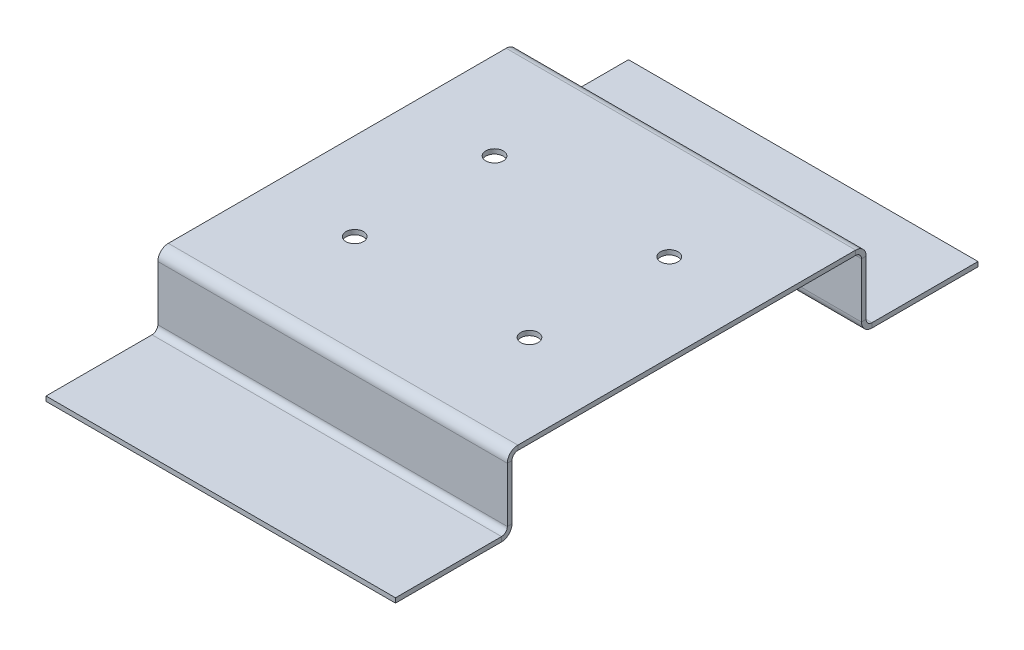
SolidWorks part; units mm, degrees
note: The reader was unsure of these and kept them because the rebuilt part matched: thickness of "Base-Flange2", "Edge-Flange1", "Edge-Flange2", "Sheet-Metal3", "Sheet-Metal4", "Sheet-Metal5", "Sheet-Metal6"; flange length of "Edge-Flange1", "Edge-Flange2".
ref_plane "Front Plane" through (0, 0, 0) normal (0, 0, 1) x (1, 0, 0)
ref_plane "Top Plane" through (0, 0, 0) normal (0, 1, 0) x (1, 0, 0)
ref_plane "Right Plane" through (0, 0, 0) normal (1, 0, 0) x (0, 0, -1)
sketch "Sketch1" plane through (0, 0, 0) normal (0, 0, 1) x (1, 0, 0)
  line L0 (0, 0) -> (20, 0)
  line L1 (20, 0) -> (20, 13)
  line L2 (20, 13) -> (80, 13)
  line L3 (80, 13) -> (80, 0)
  line L4 (80, 0) -> (100, 0)
  line L5 (0, 0.8) -> (19.2, 0.8)
  line L6 (19.2, 0.8) -> (19.2, 13.8)
  line L7 (19.2, 13.8) -> (80.8, 13.8)
  line L8 (80.8, 13.8) -> (80.8, 0.8)
  line L9 (80.8, 0.8) -> (100, 0.8)
  line L10 (0, 0) -> (0, 0.8)
  line L11 (100, 0) -> (100, 0.8)
  dimension "D2" = 20
  dimension "D3" = 20
  dimension "D4" = 60
  dimension "D5" = 13
  dimension "D1" = 0.8
sketch "Sketch7" plane through (0, 0, 0) normal (0, 1, 0) x (1, 0, 0)
  line L1 (-30, -30) -> (30, -30)
  line L2 (-30, -30) -> (-30, 30)
  line L3 (-30, 30) -> (30, 30)
  line L4 (30, -30) -> (30, 30)
  line L5 (-30, -30) -> (30, 30) construction
  line L6 (-30, 30) -> (30, -30) construction
  point P0 (0, 0)
  dimension "D1" = 60
  dimension "D2" = 60
base flange "Base-Flange2" sketch "Sketch7" thickness 0.8 reverse thickness direction no parameters "D1"=0.7366
edge flange "Edge-Flange1" sketch "Sketch14" flange profiles "Sketch14", "Sketch15" flange angle 90 flange length 13 flange position material outside bend radius 1 thickness 0.8 relief rectangular parameters "D6"=10, "D8"=1
sketch "Sketch14" plane through (0, -0.8, -30) normal (0, 0, 1) x (-1, 0, 0)
  line L2 (-30, 0) -> (-30, 12.2)
  line L3 (-30, 12.2) -> (30, 12.2)
  line L4 (30, 12.2) -> (30, 0)
  line L5 (30, 0) -> (-30, 0) construction
  line L6 (30, 0) -> (-30, 0)
sketch "Sketch15" plane through (0, -0.8, 30) normal (0, 0, -1) x (1, 0, 0)
  line L0 (30, 0) -> (-30, 0) construction
  line L1 (30, 0) -> (-30, 0)
  line L2 (30, 0) -> (30, 12.2)
  line L3 (30, 12.2) -> (-30, 12.2)
  line L4 (-30, 12.2) -> (-30, 0)
bend "EdgeBend1" bend radius 1 bend angle 90 parameters "D5"=1
bend "EdgeBend2" bend radius 1 bend angle 90 parameters "D5"=2
edge flange "Edge-Flange2" sketch "Sketch20" flange profiles "Sketch20", "Sketch21" flange angle 90 flange length 20 flange position material inside bend radius 1 thickness 0.8 relief rectangular parameters "D6"=10, "D8"=1
sketch "Sketch20" plane through (0, -13, 30.8) normal (0, -1, 0) x (1, 0, 0)
  line L2 (-30, 0) -> (-30, 19.2)
  line L3 (-30, 19.2) -> (30, 19.2)
  line L4 (30, 19.2) -> (30, 0)
  line L7 (30, 0) -> (-30, 0) construction
  line L8 (30, 0) -> (-30, 0)
sketch "Sketch21" plane through (0, -13, -30.8) normal (0, -1, 0) x (-1, 0, 0)
  line L0 (30, 0) -> (-30, 0) construction
  line L1 (30, 0) -> (-30, 0)
  line L2 (-30, 0) -> (-30, 19.2)
  line L3 (-30, 19.2) -> (30, 19.2)
  line L4 (30, 19.2) -> (30, 0)
bend "EdgeBend3" bend radius 1 bend angle 90 parameters "D5"=3
bend "EdgeBend4" bend radius 1 bend angle 90 parameters "D5"=4
sketch "Sketch22" plane through (0, 0, 0) normal (0, 1, 0) x (1, 0, 0)
  line L1 (-15, 12) -> (15, 12) construction
  line L2 (-15, 12) -> (-15, -12) construction
  line L3 (-15, -12) -> (15, -12) construction
  line L4 (15, 12) -> (15, -12) construction
  line L5 (-15, 12) -> (15, -12) construction
  line L6 (-15, -12) -> (15, 12) construction
  circle A0 centre (-15, 12) radius 1.5
  circle A1 centre (15, 12) radius 1.5
  circle A2 centre (15, -12) radius 1.5
  circle A3 centre (-15, -12) radius 1.5
  point P0 (0, 0)
  dimension "D3" = 3
  dimension "D1" = 30
  dimension "D2" = 24
extrude "Cut-Extrude2" cut sketch "Sketch22" against normal through all normal cut yes
sketch "Bend-Lines1" [suppressed] plane through (0, 0, 0) normal (0, 1, 0) x (1, 0, 0)
sketch "Bounding-Box1" [suppressed] plane through (0, 0, 0) normal (0, 1, 0) x (1, 0, 0)
sheet metal parameters "Sheet-Metal3" thickness 0.8 parameters "D1"=0.7366
flat pattern "Flat-Pattern3" [suppressed]
sketch "Bend-Lines3" plane through (0, 0, 0) normal (0, 1, 0) x (1, 0, 0)
sketch3d "Bounding-Box3" [suppressed]
  line L0 (30, -30, 0) -> (30, 30, 0) construction
  line L1 (-30, -30, 0) -> (-30, 30, 0) construction
  line L2 (30, -30, 0) -> (-30, -30, 0) construction
  line L3 (30, 30, 0) -> (-30, 30, 0) construction
sheet metal parameters "Sheet-Metal4" thickness 0.8 parameters "D1"=0.7366
flat pattern "Flat-Pattern3"
sketch "Bend-Lines3" plane through (0, 0, 0) normal (0, 1, 0) x (1, 0, 0)
  line L0 (-30, -31.0996) -> (30, -31.0996) construction
  line L1 (30, 31.0996) -> (-30, 31.0996) construction
  line L2 (-30, -31.0996) -> (30, -31.0996) construction
  line L3 (30, 31.0996) -> (-30, 31.0996) construction
sketch3d "Bounding-Box3" [suppressed]
  line L0 (-30, -43.3991, 0) -> (-30, 43.3991, 0) construction
  line L1 (30, -43.3991, 0) -> (30, 43.3991, 0) construction
  line L2 (-30, -43.3991, 0) -> (30, -43.3991, 0) construction
  line L3 (-30, 43.3991, 0) -> (30, 43.3991, 0) construction
bend of the flat pattern "Flatten-<EdgeBend1>1"
bend of the flat pattern "Flatten-<EdgeBend2>1"
sheet metal parameters "Sheet-Metal5" thickness 0.8 parameters "D1"=0.7366
flat pattern "Flat-Pattern3"
sketch "Bend-Lines3" plane through (0, 0, 0) normal (0, 1, 0) x (1, 0, 0)
  line L0 (-30, -31.0996) -> (30, -31.0996) construction
  line L1 (30, 31.0996) -> (-30, 31.0996) construction
  line L2 (-30, -31.0996) -> (30, -31.0996) construction
  line L3 (30, 31.0996) -> (-30, 31.0996) construction
  line L4 (30, 42.6987) -> (-30, 42.6987) construction
  line L5 (-30, -42.6987) -> (30, -42.6987) construction
  line L6 (30, 42.6987) -> (-30, 42.6987) construction
  line L7 (-30, -42.6987) -> (30, -42.6987) construction
sketch3d "Bounding-Box3" [suppressed]
  line L0 (-30, -61.9982, 0) -> (-30, 61.9982, 0) construction
  line L1 (30, -61.9982, 0) -> (30, 61.9982, 0) construction
  line L2 (-30, -61.9982, 0) -> (30, -61.9982, 0) construction
  line L3 (-30, 61.9982, 0) -> (30, 61.9982, 0) construction
bend of the flat pattern "Flatten-<EdgeBend1>1"
bend of the flat pattern "Flatten-<EdgeBend2>1"
bend of the flat pattern "Flatten-<EdgeBend3>1"
bend of the flat pattern "Flatten-<EdgeBend4>1"
sheet metal parameters "Sheet-Metal6" thickness 0.8 parameters "D1"=0.7366
flat pattern "Flat-Pattern3"
sketch "Bend-Lines3" plane through (0, 0, 0) normal (0, 1, 0) x (1, 0, 0)
  line L0 (-30, -30.0996) -> (30, -30.0996) construction
  line L1 (30, 30.0996) -> (-30, 30.0996) construction
  line L2 (-30, -30.0996) -> (30, -30.0996) construction
  line L3 (30, 30.0996) -> (-30, 30.0996) construction
  line L4 (30, 41.6987) -> (-30, 41.6987) construction
  line L5 (-30, -41.6987) -> (30, -41.6987) construction
  line L6 (30, 41.6987) -> (-30, 41.6987) construction
  line L7 (-30, -41.6987) -> (30, -41.6987) construction
sketch3d "Bounding-Box3" [suppressed]
  line L0 (-30, -60.9982, 0) -> (-30, 60.9982, 0) construction
  line L1 (30, -60.9982, 0) -> (30, 60.9982, 0) construction
  line L2 (-30, -60.9982, 0) -> (30, -60.9982, 0) construction
  line L3 (-30, 60.9982, 0) -> (30, 60.9982, 0) construction
bend of the flat pattern "Flatten-<EdgeBend1>1"
bend of the flat pattern "Flatten-<EdgeBend2>1"
bend of the flat pattern "Flatten-<EdgeBend3>1"
bend of the flat pattern "Flatten-<EdgeBend4>1"
